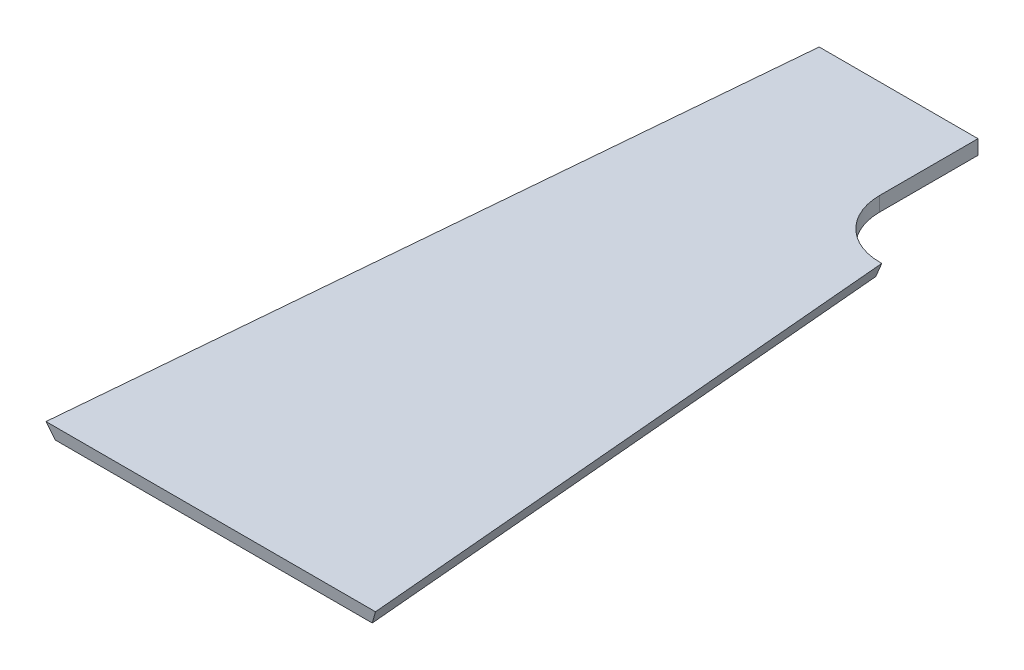
SolidWorks part; units mm, degrees
ref_plane "Ebene vorne" through (0, 0, 0) normal (0, 0, 1) x (1, 0, 0)
ref_plane "Ebene oben" through (0, 0, 0) normal (0, 1, 0) x (1, 0, 0)
ref_plane "Ebene rechts" through (0, 0, 0) normal (1, 0, 0) x (0, 0, -1)
sketch "Skizze1" plane through (0, 0, 0) normal (0, 1, 0) x (1, 0, 0)
  line L1 (-28.5, -61.5) -> (28.5, -61.5)
  line L2 (-28.5, -61.5) -> (-28.5, 61.5)
  line L3 (-28.5, 61.5) -> (28.5, 61.5)
  line L4 (28.5, -61.5) -> (28.5, 61.5)
  line L5 (-28.5, -61.5) -> (28.5, 61.5) construction
  line L6 (-28.5, 61.5) -> (28.5, -61.5) construction
  point P0 (0, 0)
  dimension "D1" = 57
  dimension "D2" = 123
extrude "Aufsatz-Linear austragen1" add sketch "Skizze1" along normal blind 2.5
sketch "Skizze2" plane through (28.5, 0, 0) normal (1, 0, 0) x (0, 0, -1)
  line L0 (-61.5, 2.5) -> (-61.5, 0)
  line L1 (55, 0) -> (-55, 0) construction
  line L2 (-61.5, 2.5) -> (-61.5, 0) construction
  line L3 (-61.5, 0) -> (-60.9686, 0)
  line L4 (-60.9686, 0) -> (-61.5, 2.5)
  dimension "D1" = 102
extrude "Schnitt-Linear austragen1" cut sketch "Skizze2" against normal through all
sketch "Skizze3" plane through (0, 2.5, 0) normal (0, 1, 0) x (1, 0, 0)
  line L0 (-28.5, -61.5) -> (-17.7389, 61.5)
  line L1 (28.5, 61.5) -> (-28.5, 61.5) construction
  line L2 (-17.7389, 61.5) -> (-28.5, 61.5)
  line L3 (-28.5, 61.5) -> (-28.5, -61.5)
  line L4 (28.5, -61.5) -> (17.7389, 61.5)
  line L5 (17.7389, 61.5) -> (28.5, 61.5)
  line L6 (28.5, 61.5) -> (28.5, -61.5)
  dimension "D1" = 95
  dimension "D2" = 95
extrude "Schnitt-Linear austragen2" cut sketch "Skizze3" against normal through all
ref_axis "Achse1" through (23.1194, 2.5, 0) along (0, -1, 0)
ref_plane "Ebene1" through (0.1756, 0, 2.0073) normal (0.0872, 0, 0.9962) x (0, -1, 0)
sketch "Skizze5" plane through (0.1756, 0, 2.0073) normal (0.0872, 0, 0.9962) x (0, -1, 0)
  line L0 (0.0086, 23.0315) -> (-2.5, 23.0315)
  line L1 (-2.5, 23.0315) -> (0, 23.0315) construction
  line L5 (0.0086, 23.0315) -> (0, 21.9959)
  line L6 (0, -33.659) -> (0, 23.0315) construction
  line L7 (0, 21.9959) -> (-2.5, 23.0315)
  line L8 (-2.5, -33.7516) -> (-2.5, 23.0315) construction
  dimension "D1" = 67.5
extrude "Schnitt-Linear austragen3" cut sketch "Skizze5" against normal through all and the other way through all
ref_axis "Achse2" through (-23.0962, 0, -0.2657) along (0, 1, 0)
ref_plane "Ebene2" through (-0.1524, 0, 1.7416) normal (-0.0872, 0, 0.9962) x (0, 1, 0)
sketch "Skizze6" plane through (-0.1524, 0, 1.7416) normal (-0.0872, 0, 0.9962) x (0, 1, 0)
  line L1 (2.5, 23.0315) -> (0, 21.9959)
  line L2 (0, -55) -> (0, 55) construction
  line L3 (0, 21.9959) -> (0, 23.0315)
  line L4 (0, 23.0315) -> (2.5, 23.0315)
  line L5 (2.5, 23.0315) -> (2.5, -33.7516) construction
  dimension "D1" = 67.5
extrude "Schnitt-Linear austragen4" cut sketch "Skizze6" against normal through all and the other way through all
ref_plane "Ebene3" through (20.9179, -12.6941, -35.8872) normal (0.9229, -0.3766, -0.0801) x (-0.0741, 0.0302, -0.9968)
sketch "Skizze8" plane through (0, 2.5, 0) normal (0, 1, 0) x (1, 0, 0)
  line L0 (17.7389, 61.5) -> (9.7389, 61.5)
  line L1 (17.7389, 61.5) -> (-17.7389, 61.5) construction
  line L2 (9.7389, 61.5) -> (9.7389, 44.5)
  line L4 (17.7389, 61.5) -> (28.5, -61.5) construction
  line L5 (20.1017, 34.4935) -> (17.7389, 61.5)
  line L6 (9.7389, 44.5) -> (9.7389, 44.4943)
  line L7 (19.7174, 34.4944) -> (20.1017, 34.4935)
  arc A1 (9.7389, 44.4943) -> (19.7174, 34.4944) centre (19.7389, 44.4943) ccw
  dimension "D1" = 10
  dimension "D2" = 8
  dimension "D3" = 17
extrude "Schnitt-Linear austragen5" cut sketch "Skizze8" against normal through all
